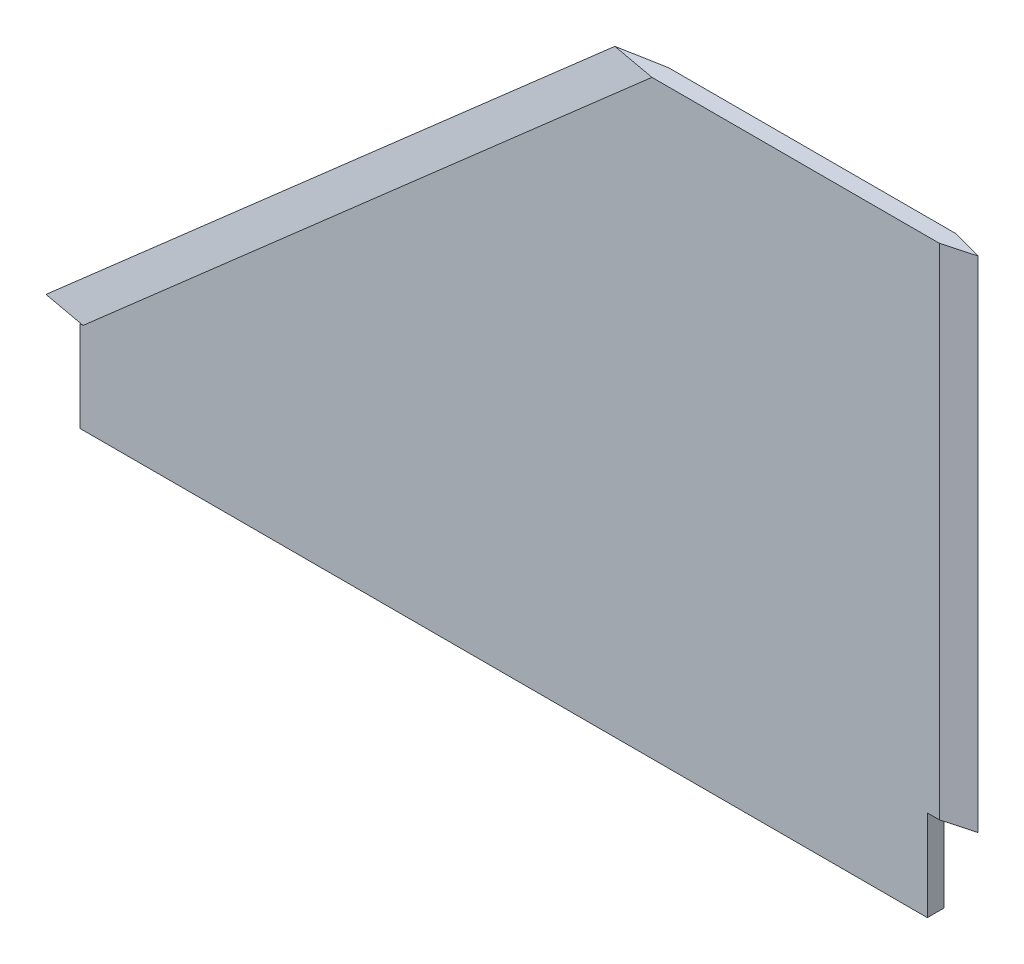
SolidWorks part; units mm, degrees
material "Hexcel AS4C (3000 Filaments)"
ref_plane "Front Plane" through (0, 0, 0) normal (0, 0, 1) x (1, 0, 0)
ref_plane "Top Plane" through (0, 0, 0) normal (0, 1, 0) x (1, 0, 0)
ref_plane "Right Plane" through (0, 0, 0) normal (1, 0, 0) x (0, 0, -1)
sketch "Sketch1" plane through (0, 0, 0) normal (0, 0, 1) x (1, 0, 0)
  line L0 (-140, 0) -> (-154, 0)
  line L1 (-140, -30) -> (140, -30)
  line L2 (-140, -30) -> (-140, 0)
  line L4 (140, -30) -> (140, 0)
  line L5 (-154, 0) -> (34, 165)
  line L6 (34, 165) -> (154, 165)
  line L7 (154, 165) -> (154, 0)
  line L8 (154, 0) -> (140, 0)
  line L9 (-140, 0) -> (140, 0)
  dimension "D1" = 30
  dimension "D2" = 308
  dimension "D3" = 280
  dimension "D4" = 165
  dimension "D5" = 120
extrude "Boss-Extrude1" add sketch "Sketch1" along normal blind 2.75 and the other way blind 2.75 contours L9 L2 L1 L4 | L0 L9 L8 L7 L6 L5 region at (0, -15, 0) region at (40.1184, 70.4206, 0)
sketch "Sketch2" plane through (0, 165, 0) normal (0, 1, 0) x (1, 0, 0)
  line L0 (34, 0) -> (49, -2.75)
  line L1 (34, 2.75) -> (34, -2.75) construction
  line L2 (34, -2.75) -> (154, -2.75) construction
  line L3 (49, -2.75) -> (34, -2.75)
  line L4 (34, -2.75) -> (34, 0)
  line L5 (34, 2.75) -> (34, 0)
  line L6 (49, 2.75) -> (34, 0)
  line L7 (34, 2.75) -> (154, 2.75) construction
  line L8 (34, 2.75) -> (49, 2.75)
  line L9 (49, 2.75) -> (49, -2.75) construction
  line M3 (34, 2.75) -> (34, -2.75)
  line M4 (34, -2.75) -> (154, -2.75)
  line M6 (154, 2.75) -> (34, 2.75)
  dimension "D1" = 15
extrude "Cut-Extrude1" cut sketch "Sketch2" along direction (0.7516, 0.6596, 0) on the side against the normal up to surface (165 mm away) contours L0 M3 M4 | L6 M6 M3 region at (39, 165, 1.8333) region at (39, 165, -1.8333) up to face at (147, 0, 0)
sketch "Sketch3" plane through (0, 165, 0) normal (0, 1, 0) x (1, 0, 0)
  line L0 (144, 2.75) -> (154, 2.75)
  line L1 (49, 2.75) -> (154, 2.75) construction
  line L2 (154, -2.75) -> (154, 0)
  line L3 (154, -2.75) -> (144, -2.75)
  line L4 (49, -2.75) -> (154, -2.75) construction
  line L5 (144, -2.75) -> (154, 0)
  line L6 (154, 0) -> (144, 2.75)
  line L7 (144, 2.75) -> (144, -2.75) construction
  line L8 (154, 2.75) -> (154, 0)
  line M5 (49, -2.75) -> (154, -2.75)
  line M6 (154, -2.75) -> (154, 2.75)
  line M7 (154, 2.75) -> (49, 2.75)
  dimension "D1" = 10
extrude "Cut-Extrude2" cut sketch "Sketch3" against normal up to surface (165 mm away) contours L5 M5 M6 | L6 M6 M7 region at (150.6667, 165, 1.8333) region at (150.6667, 165, -1.8333) up to face at (147, 0, 0)
sketch "Sketch4" plane through (0, 0, 2.75) normal (0, 0, 1) x (1, 0, 0)
  line L0 (-154, 0) -> (154, 0)
  line L1 (34, 165) -> (154, 165)
  line L2 (94, 165) -> (0, 0)
  line L3 (140, -30) -> (140, 0) construction
  dimension "D1" = 189.8973
  dimension "D2" = 14
  dimension "D3" = 188
